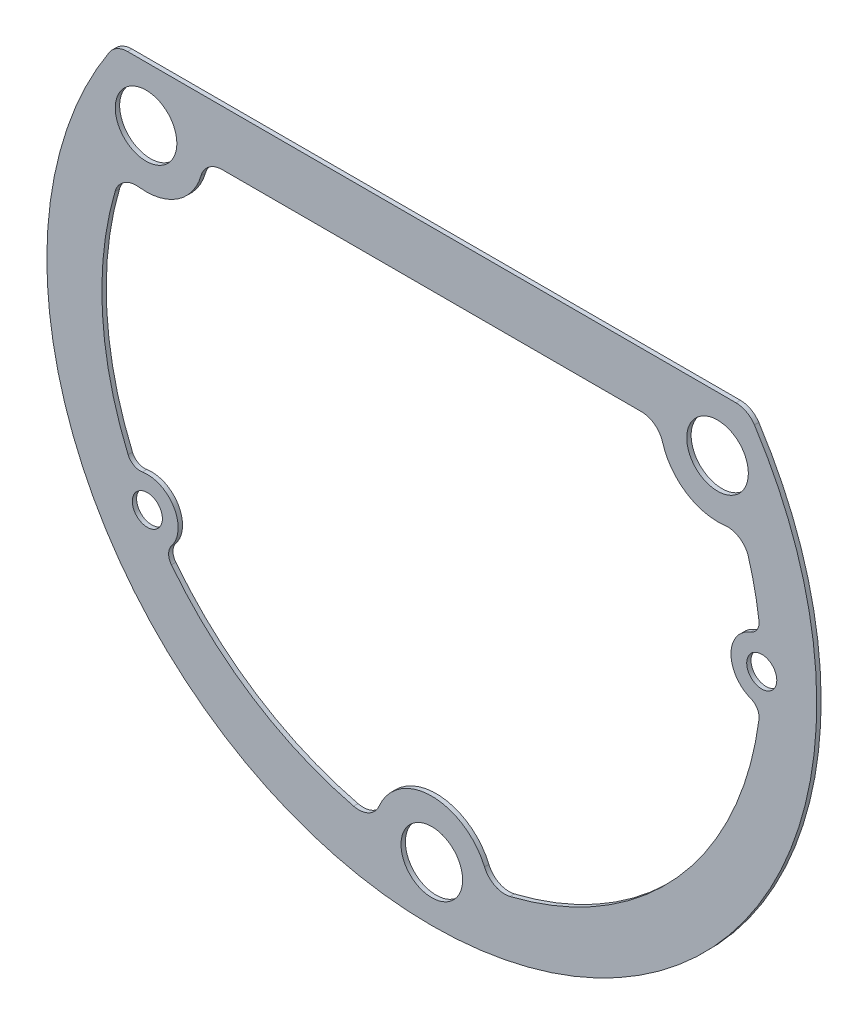
SolidWorks part; units mm, degrees
material "Картон А-1 ГОСТ 9347-60"
ref_plane "Спереди" through (0, 0, 0) normal (0, 0, 1) x (1, 0, 0)
ref_plane "Сверху" through (0, 0, 0) normal (0, 1, 0) x (1, 0, 0)
ref_plane "Справа" through (0, 0, 0) normal (1, 0, 0) x (0, 0, -1)
other "Configuration Table"
sketch "Эскиз1" plane through (0, 0, 0) normal (0, 0, 1) x (1, 0, 0)
  line L0 (-69.1466, 50) -> (69.1466, 50)
  line L3 (-47.6584, 37.5033) -> (47.6584, 37.5033)
  arc A0 (-66.566, 24.6041) -> (-52.4616, 33.8922) centre (-64.95, 37.5033) ccw
  arc A1 (52.4616, 33.8922) -> (66.566, 24.6041) centre (64.95, 37.5033) ccw
  arc A2 (11.9787, -69.9493) -> (-11.9787, -69.9493) centre (0, -75) ccw
  arc A3 (-59.1933, -46.056) -> (-17.7706, -72.8643) centre (0, 0) ccw
  arc A4 (-59.1761, -42.3496) -> (-65.792, -31.092) centre (-64.6607, -38) ccw
  arc A5 (72.4753, 6.5289) -> (72.4753, -6.5289) centre (75, 0) ccw
  arc A8 (17.7706, -72.8643) -> (74.3681, -9.7156) centre (0, 0) ccw
  arc A9 (74.3681, 9.7156) -> (71.9866, 21.046) centre (0, 0) ccw
  arc A10 (-71.9866, 21.046) -> (-69.0384, -29.3036) centre (0, 0) ccw
  arc A11 (-73.3373, 47.7273) -> (73.3373, 47.7273) centre (0, 0) ccw
  arc A12 (73.3373, 47.7273) -> (69.1466, 50) centre (69.1466, 45) ccw
  arc A13 (-69.1466, 50) -> (-73.3373, 47.7273) centre (-69.1466, 45) ccw
  arc A14 (17.7706, -72.8643) -> (11.9787, -69.9493) centre (16.5859, -68.0067) cw
  arc A15 (-11.9787, -69.9493) -> (-17.7706, -72.8643) centre (-16.5859, -68.0067) cw
  arc A16 (71.9866, 21.046) -> (66.566, 24.6041) centre (67.1875, 19.6429) ccw
  arc A17 (47.6584, 37.5033) -> (52.4616, 33.8922) centre (47.6584, 32.5033) cw
  arc A18 (-71.9866, 21.046) -> (-66.566, 24.6041) centre (-67.1875, 19.6429) cw
  arc A19 (-47.6584, 37.5033) -> (-52.4616, 33.8922) centre (-47.6584, 32.5033) ccw
  arc A20 (74.3681, -9.7156) -> (72.4753, -6.5289) centre (71.3933, -9.3269) ccw
  arc A21 (74.3681, 9.7156) -> (72.4753, 6.5289) centre (71.3933, 9.3269) cw
  arc A22 (-59.1761, -42.3496) -> (-59.1933, -46.056) centre (-56.8255, -44.2138) ccw
  arc A23 (-65.792, -31.092) -> (-69.0384, -29.3036) centre (-66.2768, -28.1315) cw
  circle A24 centre (-64.95, 37.5033) radius 7
  circle A25 centre (64.95, 37.5033) radius 7
  circle A26 centre (0, -75) radius 7
  dimension "D1" = 5
  dimension "D2" = 3
  dimension "D3" = 75
  dimension "D4" = 175
  dimension "D14" = 14
  dimension "D5" = 17.7706
  dimension "D6" = 47.6584
  dimension "D7" = 69.1466
  dimension "D8" = 71.9866
  dimension "D9" = 74.3681
  dimension "D10" = 47.6584
  dimension "D11" = 59.1933
  dimension "D12" = 69.0384
  dimension "D13" = 37.5033
  dimension "D15" = 64.95
  dimension "D16" = 64.95
  dimension "D17" = 75
  dimension "D18" = 75
  dimension "D19" = 75
extrude "Бобышка-Вытянуть1" add sketch "Эскиз1" along normal blind 1
ref_plane "Плоскость1" through (0, 0, -18) normal (0, 0, -1) x (-1, 0, 0)
ref_plane "Плоскость2" through (0, 0, 25) normal (0, 0, 1) x (1, 0, 0)
sketch "Эскиз2" plane through (0, 0, -18) normal (0, 0, -1) x (-1, 0, 0)
  circle A0 centre (-75, 0) radius 3.75
  circle A1 centre (64.6607, -38) radius 3.75
  dimension "D1" = 7.5
  dimension "D2" = 7.5
sketch "Эскиз3" plane through (0, 0, 25) normal (0, 0, 1) x (1, 0, 0)
  circle A0 centre (-64.6607, -38) radius 3
  circle A1 centre (75, 0) radius 3
  dimension "D1" = 6
ref_plane "Плоскость3" through (0, -38, 0) normal (0, 1, 0) x (1, 0, 0)
loft "Вырез-По сечениям1" cut section "Эскиз2" section "Эскиз3" connector at (-60.9107, -38.0003, -18) connector at (-61.6607, -38, 25)
loft "Вырез-По сечениям2" cut section "Эскиз2<4>" section "Эскиз3<4>" connector at (71.25, 0, -18) connector at (72, 0.0018, 25)
sketch "Эскиз2<4>" plane through (0, 0, -18) normal (0, 0, -1) x (-1, 0, 0) same geometry as "Эскиз2"
sketch "Эскиз3<4>" plane through (0, 0, 25) normal (0, 0, 1) x (1, 0, 0) same geometry as "Эскиз3"
